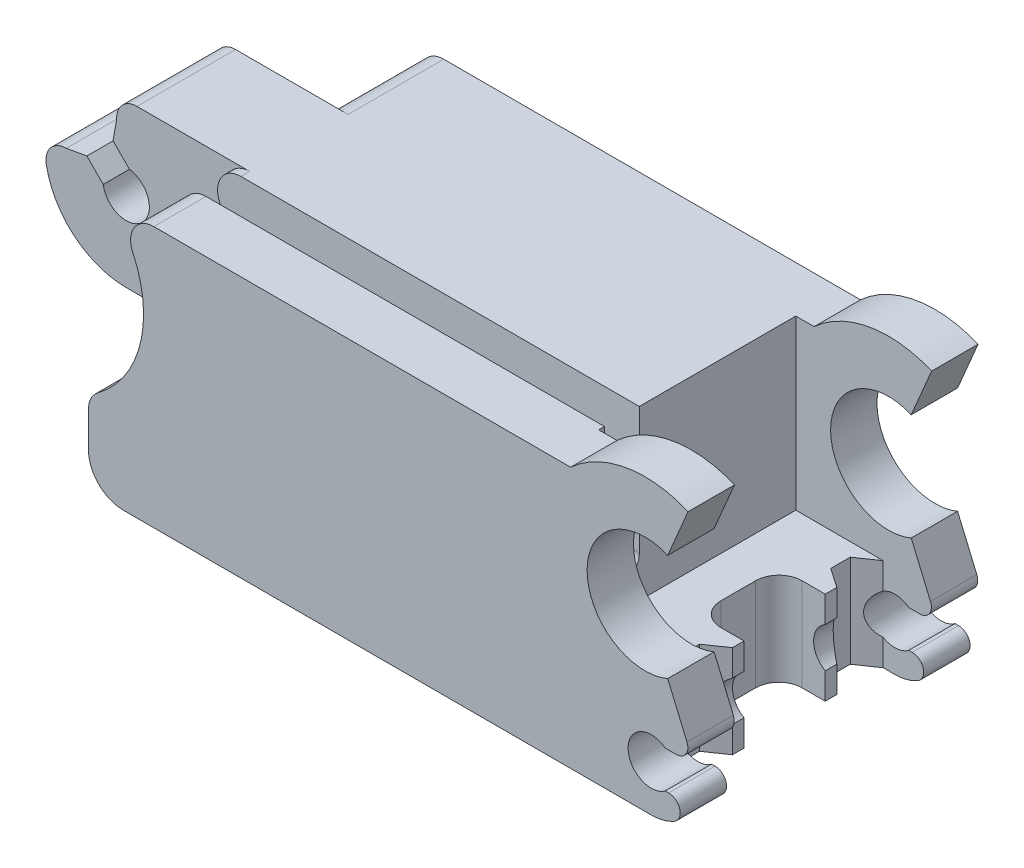
SolidWorks part; units mm, degrees
ref_plane "Front Plane" through (0, 0, 0) normal (0, 0, 1) x (1, 0, 0)
ref_plane "Top Plane" through (0, 0, 0) normal (0, 1, 0) x (1, 0, 0)
ref_plane "Right Plane" through (0, 0, 0) normal (1, 0, 0) x (0, 0, -1)
sketch "Sketch1" plane through (0, 0, 0) normal (0, 0, 1) x (1, 0, 0)
  line L0 (0, 0) -> (9.5, 0) construction
  line L1 (-62.5, 9.5) -> (9.5, 9.5)
  line L2 (-62.5, 9.5) -> (-62.5, -15.5)
  line L3 (-62.5, -15.5) -> (9.5, -15.5)
  line L4 (9.5, 9.5) -> (9.5, -15.5)
  line L5 (0, 0) -> (3.7119, 8.7448) construction
  line L6 (3.7119, 8.7448) -> (1.856, 4.3724)
  line L7 (3.7119, -8.7448) -> (1.856, -4.3724)
  line L8 (1.736, -9.9) -> (1.736, -13.1)
  line L9 (1.736, -9.9) -> (4.2021, -9.9)
  line L10 (1.736, -13.1) -> (4.2021, -13.1)
  line L11 (-52.7172, 1.9799) -> (-54.9799, -0.2828)
  line L12 (-62.5, -15.5) -> (-43, -15.5)
  line L13 (-62.5, -15.5) -> (-62.5, -6.5)
  line L16 (-52.7172, 1.9799) -> (-54.1314, 3.3941)
  line L17 (-58.1668, 0.8188) -> (-59.6208, 2.2728)
  line L18 (-53, 0) -> (-53.8485, 0.8485) construction
  line L19 (-56.3941, 1.1314) -> (-58.1668, 0.8188)
  line L20 (-53, 7) -> (-6.4226, 7)
  line L21 (-54.9799, -0.2828) -> (-56.3941, 1.1314)
  line L22 (-54.1314, 3.3941) -> (-53.8188, 5.1668)
  line L23 (-53.8188, 5.1668) -> (-55.2728, 6.6208)
  line L24 (-53, -7) -> (-43, -7)
  line L25 (-43, -7) -> (-43, -15.5)
  line L26 (4.2021, -9.9) -> (3.7119, -8.7448)
  line L27 (-43, -7) -> (-43, 0) construction
  line L28 (-48, -7) -> (-48, -15.5)
  line L29 (-53, 0) -> (-55, 0) construction
  circle A0 centre (0, 0) radius 2 construction
  circle A1 centre (-53, 0) radius 2
  circle A2 centre (0, 0) radius 5
  circle A3 centre (0, 0) radius 9.5
  circle A4 centre (0.536, -11.5) radius 2
  circle A5 centre (0.536, -11.5) radius 4
  circle A6 centre (-53, 0) radius 7
  circle A8 centre (-53, 0) radius 6 construction
  circle A9 centre (-53, 0) radius 6.5 construction
  point P39 (4.536, -11.5)
  dimension "D1" = 4
  dimension "D2" = 4
  dimension "D4" = 10
  dimension "D9" = 4
  dimension "D13" = 8
  dimension "D20" = 12
  dimension "D23" = 19
  dimension "D3" = 53
  dimension "D5" = 25
  dimension "D6" = 9.5
  dimension "D8" = 67
  dimension "D10" = 2
  dimension "D12" = 3.2
  dimension "D16" = 3.2
  dimension "D14" = 2
  dimension "D15" = 4.536
  dimension "D24" = 10
  dimension "D21" = 5
  dimension "D18" = 125
  dimension "D19" = 1.8
  dimension "D25" = 45
  dimension "D7" = 4.5
  dimension "D11" = 2
  dimension "D17" = 5
  dimension "D22" = 0.5
extrude "Boss-Extrude1" add sketch "Sketch1" along normal mid plane 25 contours A6 L23 L22 L16 A1 L21 L19 L17 | A6 L24 L25 L3 A5 A3 L20 | A5 A3 L7 A2 L6 | A3 A5 | L9 A5 A3 L10 A4 | A5 L26 A3 region at (1.8485, 9.0856, 0) region at (-26.1779, -4.322, 0) region at (-48.1903, 4.8097, 0) region at (0.3999, -8.5786, 0) region at (0.4428, -9.4998, 0) region at (3.7778, -9.0652, 0)
fillet "Fillet1" radius 1 2 edges at (4.2021, -13.1, 0) (4.2021, -9.9, 0)
sketch "Sketch3" plane through (0, 0, 0) normal (0, 0, 1) x (1, 0, 0)
  line L0 (-43, -15.5) -> (0.536, -15.5) construction
  line L1 (-8, 10.2107) -> (7.5521, 10.2107)
  line L2 (-8, 10.2107) -> (-8, -15.5)
  line L3 (-8, -15.5) -> (7.5521, -15.5)
  line L4 (7.5521, 10.2107) -> (7.5521, -15.5)
  dimension "D1" = 8
extrude "Cut-Extrude1" cut sketch "Sketch3" against normal offset from surface 4 and the other way offset from surface 4 contours L4 L1 L2 L3 region at (-0.2239, -2.6446, 0) up to face at (-27.411, -3.1826, -12.5) other way up to face at (-27.411, -3.1826, 12.5)
sketch "Sketch5" plane through (0, 0, 12.5) normal (0, 0, 1) x (1, 0, 0)
  line L0 (-53, 7) -> (-6.4226, 7) construction
  line L1 (-43, -7) -> (-73.6432, -7)
  line L2 (-43, -7) -> (-43, 7)
  line L3 (-43, 7) -> (-73.6432, 7)
  line L4 (-73.6432, -7) -> (-73.6432, 7)
extrude "Cut-Extrude2" cut sketch "Sketch5" against normal offset from surface (8.25 mm away) 4.25 up to face at (-0.7087, -5.8791, 8.5) offset beyond the face yes
sketch "Sketch6" plane through (0, 0, -12.5) normal (0, 0, -1) x (-1, 0, 0)
  line L8 (43, -7) -> (73.6432, -7)
  line L9 (73.6432, -7) -> (73.6432, 7)
  line L10 (73.6432, 7) -> (43, 7)
  line L11 (43, 7) -> (43, -7)
  line L12 (43, -7) -> (73.6432, -7)
  line L13 (73.6432, -7) -> (73.6432, 7)
  line L14 (73.6432, 7) -> (43, 7)
  line L15 (43, 7) -> (43, -7)
  line M10 (43, -7) -> (53, -7)
  arc M11 (53, -7) -> (59.6208, 2.2728) centre (53, 0) ccw
  line M12 (59.6208, 2.2728) -> (58.1668, 0.8188)
  line M13 (58.1668, 0.8188) -> (56.3941, 1.1314)
  line M14 (56.3941, 1.1314) -> (54.9799, -0.2828)
  arc M15 (54.9799, -0.2828) -> (52.7172, 1.9799) centre (53, 0) cw
  line M16 (52.7172, 1.9799) -> (54.1314, 3.3941)
  line M17 (54.1314, 3.3941) -> (53.8188, 5.1668)
  line M18 (53.8188, 5.1668) -> (55.2728, 6.6208)
  arc M19 (55.2728, 6.6208) -> (53, 7) centre (53, 0) ccw
  line M20 (53, 7) -> (6.4226, 7)
  dimension "D1" = 0
extrude "Cut-Extrude3" cut sketch "Sketch6" against normal offset from surface (8.25 mm away) 4.25 contours M10 M11 M12 M13 M14 M15 M16 M17 M18 M19 M20 region at (-49.9173, -0.455, -12.5) up to face at (-0.7087, -5.8791, -8.5) offset beyond the face yes
sketch "Sketch7" plane through (0, 0, 0) normal (0, 0, 1) x (1, 0, 0)
  line L9 (-55.2728, 6.6208) -> (-53.8188, 5.1668)
  line L10 (-55.2728, 6.6208) -> (-53.8188, 5.1668)
  line L11 (-53.8188, 5.1668) -> (-54.1314, 3.3941)
  line L12 (-53.8188, 5.1668) -> (-54.1314, 3.3941)
  line L13 (-54.1314, 3.3941) -> (-52.7172, 1.9799)
  line L14 (-54.1314, 3.3941) -> (-52.7172, 1.9799)
  line L15 (-43, 7) -> (-53, 7)
  line L16 (-43, -7) -> (-43, 7)
  line L17 (-54.9799, -0.2828) -> (-56.3941, 1.1314)
  line L25 (-43, -7) -> (-43, 7)
  line L27 (-54.9799, -0.2828) -> (-56.3941, 1.1314)
  line L28 (-56.3941, 1.1314) -> (-58.1668, 0.8188)
  line L29 (-56.3941, 1.1314) -> (-58.1668, 0.8188)
  line L30 (-58.1668, 0.8188) -> (-59.6208, 2.2728)
  line L31 (-58.1668, 0.8188) -> (-59.6208, 2.2728)
  line L32 (-43, 7) -> (-53, 7)
  line L34 (-53, -7) -> (-43, -7)
  line L37 (-53, -7) -> (-43, -7)
  arc A1 (-53, 7) -> (-55.2728, 6.6208) centre (-53, 0) ccw
  arc A5 (-53, 7) -> (-55.2728, 6.6208) centre (-53, 0) ccw
  arc A9 (-54.9799, -0.2828) -> (-52.7172, 1.9799) centre (-53, 0) ccw
  arc A10 (-54.9799, -0.2828) -> (-52.7172, 1.9799) centre (-53, 0) ccw
  arc A11 (-59.6208, 2.2728) -> (-53, -7) centre (-53, 0) ccw
  arc A12 (-59.6208, 2.2728) -> (-53, -7) centre (-53, 0) ccw
  dimension "D1" = 0
fillet "Fillet2" radius 1.75 2 edges at (-59.6208, 2.2728, 0) (-55.2728, 6.6208, 0)
sketch "Sketch8" [suppressed] plane through (0, 0, -4.25) normal (0, 0, 1) x (1, 0, 0)
  line L0 (-53, 7) -> (-43, 7)
  line L1 (-43, 7) -> (-43, -7)
  line L2 (-43, -7) -> (-53, -7)
  arc A0 (-54.9799, -0.2828) -> (-52.7172, 1.9799) centre (-53, 0) ccw construction
  arc A1 (-54.9799, -0.2828) -> (-52.7172, 1.9799) centre (-53, 0) ccw
  circle A2 centre (-53, 0) radius 6 construction
  circle A3 centre (-53, 0) radius 7
  dimension "D1" = 12
sketch "Sketch10" plane through (0, 0, 4.25) normal (0, 0, 1) x (1, 0, 0)
  line L1 (-48, -7) -> (-48, -15.5) construction
  line L2 (-48, -7) -> (-48, -15.5)
  line L3 (-43, 7) -> (-46.2131, 7)
  line L6 (-52.0708, 7) -> (-43, 7) construction
  line L7 (-43, 7) -> (-43, -15.5)
  line L8 (-43, -15.5) -> (-48, -15.5)
  arc A0 (3.7119, 8.7448) -> (-6.4226, 7) centre (0, 0) ccw construction
  arc A1 (-54.9799, -0.2828) -> (-52.7172, 1.9799) centre (-53, 0) ccw construction
  arc A2 (3.7119, 8.7448) -> (-6.4226, 7) centre (0, 0) ccw construction
  arc A3 (-54.9799, -0.2828) -> (-52.7172, 1.9799) centre (-53, 0) ccw construction
  circle A4 centre (-53, 0) radius 9.75
  line M9 (-53, -7) -> (-43, -7)
  line M10 (-43, -7) -> (-43, 7)
  line M11 (-43, 7) -> (-52.0708, 7)
  dimension "D1" = 9.5
  dimension "D2" = 19.5
extrude "Boss-Extrude3" add sketch "Sketch10" along normal up to surface (8.25 mm away) contours A4 M9 M10 M11 | A4 L2 L8 L7 M9 region at (-45.4396, -11.3712, 4.25) region at (-43.889, -3.8566, 4.25) up to face at (-6.0933, -5.8791, 12.5)
sketch "Sketch41" plane through (0, 0, -4.25) normal (0, 0, -1) x (-1, 0, 0)
  line L0 (43, 7) -> (46.2131, 7) construction
  line L1 (43, 7) -> (43, -15.5) construction
  line L2 (43, -15.5) -> (48, -15.5) construction
  line L3 (48, -7) -> (48, -15.5) construction
  line L4 (43, 7) -> (46.2131, 7)
  line L5 (43, 7) -> (43, -15.5)
  line L6 (43, -15.5) -> (48, -15.5)
  line L7 (48, -7) -> (48, -15.5)
  circle A1 centre (53, 0) radius 9.75
  circle A2 centre (53, 0) radius 9.75
  line M10 (52.0708, 7) -> (43, 7)
  line M11 (43, 7) -> (43, -7)
  line M12 (43, -7) -> (53, -7)
  dimension "D1" = 0
extrude "Boss-Extrude6" add sketch "Sketch41" along normal up to surface (8.25 mm away) contours A2 L5 L6 L7 M12 | A2 M10 M11 M12 region at (-44.6065, 6.8564, -4.25) region at (-45.4396, -11.3712, -4.25) up to face at (-6.0933, -5.8791, -12.5)
fillet "Fillet4" radius 2 4 edges at (-48, -8.3703, 8.375) (-46.2131, 7, 8.375) (-48, -8.3703, -8.375) (-46.2131, 7, -8.375)
ref_plane "Plane1" through (0, 0, 6.5) normal (0, 0, 1) x (1, 0, 0)
sketch "Sketch11" plane through (0, 0, 6.5) normal (0, 0, -1) x (-1, 0, 0)
  line L0 (51.8208, 5.4642) -> (1.1792, -5.4642)
  arc A0 (52.7172, 1.9799) -> (54.9799, -0.2828) centre (53, 0) ccw construction
  arc A1 (52.7172, 1.9799) -> (54.9799, -0.2828) centre (53, 0) ccw construction
  arc A2 (-1.9537, -4.6025) -> (-1.9537, 4.6025) centre (0, 0) ccw construction
  arc A3 (-1.9537, -4.6025) -> (-1.9537, 4.6025) centre (0, 0) ccw construction
  circle A4 centre (53, 0) radius 5 construction
  circle A5 centre (0, 0) radius 5 construction
  circle A6 centre (53, 0) radius 5.59 construction
  circle A7 centre (0, 0) radius 5.59 construction
  dimension "D3" = 0.59
sweep "Cut-Sweep1" cut path "Sketch11" circular profile diameter 3 parameters "D3"=3
fillet "Fillet6" radius 3 2 edges at (-48, -15.5, 8.375) (-48, -15.5, -8.375)
sketch "Sketch24" plane through (0, 0, 0) normal (0, 0, 1) x (1, 0, 0)
  line L0 (-45, -15.5) -> (0.536, -15.5) construction
  line L1 (-45, -15.5) -> (0.536, -15.5) construction
  line L6 (-24.5, -13.5) -> (-24.5, -15.5) construction
  line L7 (-11.5, -13.5) -> (-11.5, -15.5) construction
  line L8 (-41.5, -13.5) -> (-41.5, -15.5)
  line L9 (-28.5, -13.5) -> (-28.5, -15.5)
  line L10 (-41.5, -15.5) -> (-28.5, -15.5)
  line L11 (-24.5, -15.5) -> (-11.5, -15.5) construction
  line L12 (-35, -7) -> (-48, -7)
  line L13 (-48, -9.4373) -> (-48, -12.5) construction
  line L14 (-48, -7) -> (-48, -15.5)
  line L15 (-48, -15.5) -> (-28.5, -15.5)
  circle A0 centre (-18, -13.5) radius 2 construction
  arc A5 (-54.9799, -0.2828) -> (-52.7172, 1.9799) centre (-53, 0) ccw construction
  arc A6 (-54.9799, -0.2828) -> (-52.7172, 1.9799) centre (-53, 0) ccw construction
  circle A7 centre (-35, -13.5) radius 2 construction
  arc A8 (-11.5, -13.5) -> (-24.5, -13.5) centre (-18, -13.5) ccw construction
  arc A9 (-28.5, -13.5) -> (-41.5, -13.5) centre (-35, -13.5) ccw
  circle A10 centre (-18, -13.5) radius 2.2 construction
  circle A11 centre (-35, -13.5) radius 2.2
  dimension "D1" = 4
  dimension "D2" = 18
  dimension "D3" = 4.5
  dimension "D4" = 18
  dimension "D5" = 0.2
extrude "Cut-Extrude6" cut sketch "Sketch24" against normal mid plane 8.5 contours A10 L11 L7 A8 L6 | A11 L10 L9 A9 L8 | A9 L12 L14 L15 L8 region at (-39.4864, -9.0136, 0) region at (-44.0872, -10.8555, 0)
sketch "Sketch45" plane through (0, 0, 0) normal (0, 0, 1) x (1, 0, 0)
  line L0 (3.612, -8.5093) -> (1.9537, -4.6025) construction
  line L1 (3.612, -8.5093) -> (1.9537, -4.6025)
  arc A0 (1.736, -9.9) -> (1.736, -13.1) centre (0.536, -11.5) ccw construction
  arc A1 (1.736, -9.9) -> (1.736, -13.1) centre (0.536, -11.5) ccw
sketch "Sketch47" plane through (0, 7, 0) normal (0, 1, 0) x (1, 0, 0)
  line L0 (-8, -5) -> (-44.0122, -5) construction
  line L1 (-5.5113, -5) -> (-48.8713, -5)
  line L2 (-44.0122, -8) -> (-8, -8) construction
  line L3 (-48.8713, -8) -> (-5.5113, -8)
  line L4 (-48.8713, -8) -> (-48.8713, -5)
  line L5 (-5.5113, -5) -> (-5.5113, -8)
extrude "Cut-Extrude7" cut sketch "Sketch47" against normal up to surface (11.5293 mm away) up to face at (-43.9108, 3.7419, 6.6784)
sketch "Sketch50" plane through (0, 0, 8.5) normal (0, 0, -1) x (-1, 0, 0)
  line L0 (0.464, -13.2321) -> (0.464, -15.5)
  line L1 (8, -15.5) -> (-0.536, -15.5) construction
  line L2 (8, 7) -> (8, -15.5) construction
  line L3 (8, 7) -> (8, -15.5)
  line L4 (0.464, -15.5) -> (8, -15.5)
  line L5 (0.464, -9.7679) -> (0.464, -7.5)
  line L6 (0.464, -7.5) -> (8, -7.5)
  arc A0 (-1.736, -13.1) -> (-1.736, -9.9) centre (-0.536, -11.5) ccw construction
  arc A1 (-1.736, -13.1) -> (-1.736, -9.9) centre (-0.536, -11.5) ccw
  arc M11 (-1.736, -9.9) -> (-1.736, -13.1) centre (-0.536, -11.5) cw
  line M15 (-0.536, -15.5) -> (8, -15.5)
  line M16 (8, -15.5) -> (8, 7)
  dimension "D1" = 4
  dimension "D2" = 4
extrude "Boss-Extrude7" add sketch "Sketch50" along normal up to vertex contours L6 L5 L0 M11 M15 M16 region at (-4.3746, -11.5, 8.5) up to point (0.536, -15.5, -8.5)
sketch "Sketch51" plane through (0, -15.5, 0) normal (0, -1, 0) x (1, 0, 0)
  line L0 (-0.464, -8.5) -> (-0.464, 8.5) construction
  line L1 (-0.464, -8.5) -> (-0.464, 8.5)
  line L2 (-2.144, 5.66) -> (-2.144, 7.34)
  line L3 (-2.144, 7.34) -> (-0.464, 8.5)
  line L4 (-2.144, 6.5) -> (-0.464, 6.5) construction
  line L5 (-2.144, 5.66) -> (-0.464, 4.5)
  line L6 (-0.464, 0) -> (-3.9441, 0) construction
  line L7 (-2.144, -5.66) -> (-0.464, -4.5)
  line L8 (-2.144, -5.66) -> (-2.144, -7.34)
  line L9 (-2.144, -7.34) -> (-0.464, -8.5)
  line L12 (-0.464, 3.5) -> (-0.464, -4)
  line L13 (-0.464, 3.5) -> (-4.464, 3.5)
  line L14 (-0.464, 3.5) -> (-0.464, -3.5)
  line L15 (-0.464, -3.5) -> (-4.464, -3.5)
  line L16 (-4.464, 3.5) -> (-4.464, -3.5)
  point P2 (-2.144, 6.5)
  point P6 (-2.144, 6.5)
  point P17 (-4.464, 0)
  line M26 (-0.464, -8.5) -> (-0.464, 8.5)
  dimension "D1" = 2
  dimension "D2" = 1.68
  dimension "D3" = 1.68
  dimension "D4" = 7
  dimension "D5" = 4
extrude "Cut-Extrude8" cut sketch "Sketch51" against normal up to surface (8 mm away) contours L2 L5 L1 L3 | L8 L9 L7 M26 | L13 L16 L15 L12 region at (-1.1896, -15.5, -6.5) region at (-1.1896, -15.5, 6.5) region at (-2.464, -15.5, 0) up to face at (-4.232, -7.5, 0)
fillet "Fillet10" radius 2 2 edges at (-4.464, -11.5, 3.5) (-4.464, -11.5, -3.5)
equation "\"mainSnapAngle\"= 67deg"
equation "\"D8@Sketch1\"=\"mainSnapAngle\""
equation "\"jointDistance\"= 53mm"
equation "\"mountBearingOD\"= 10mm"
equation "\"D3@Sketch1\"=\"jointDistance\""
equation "\"D4@Sketch1\"=\"mountBearingOD\""
equation "\"shaftDiameter\"= 4mm"
equation "\"D12@Sketch1\"=\"shaftDiameter\"*0.8"
equation "\"D2@Sketch1\"=\"shaftDiameter\""
equation "\"D1@Sketch1\"=\"shaftDiameter\""
equation "\"D16@Sketch1\"=\"D2@Sketch1\"*0.8"
equation "\"UgrooveOD\"= 12mm"
equation "\"D20@Sketch1\"=\"UgrooveOD\""
equation "\"D1@Sketch8\"=\"UgrooveOD\""
equation "\"D24@Sketch1\"= \"D23@Sketch1\" / 2 + 0.5"
equation "\"D2@Sketch10\"=\"D1@Sketch10\"*2+0.5"
equation "\"grooveDiameter\"= 10mm"
equation "\"tendonDiameter\"= 1.18mm"
equation "\"D3@Sketch11\"=\"tendonDiameter\"/2"
equation "\"D1@Sketch11\"=\"grooveDiameter\""
equation "\"D1@Sketch3\"=\"UgrooveOD\"/2+2"
equation "\"D2@Sketch50\"=\"D1@Sketch50\""
equation "\"D2@Sketch51\"=\"tendonDiameter\" +0.5"
equation "\"D3@Sketch51\"=\"D2@Sketch51\""
